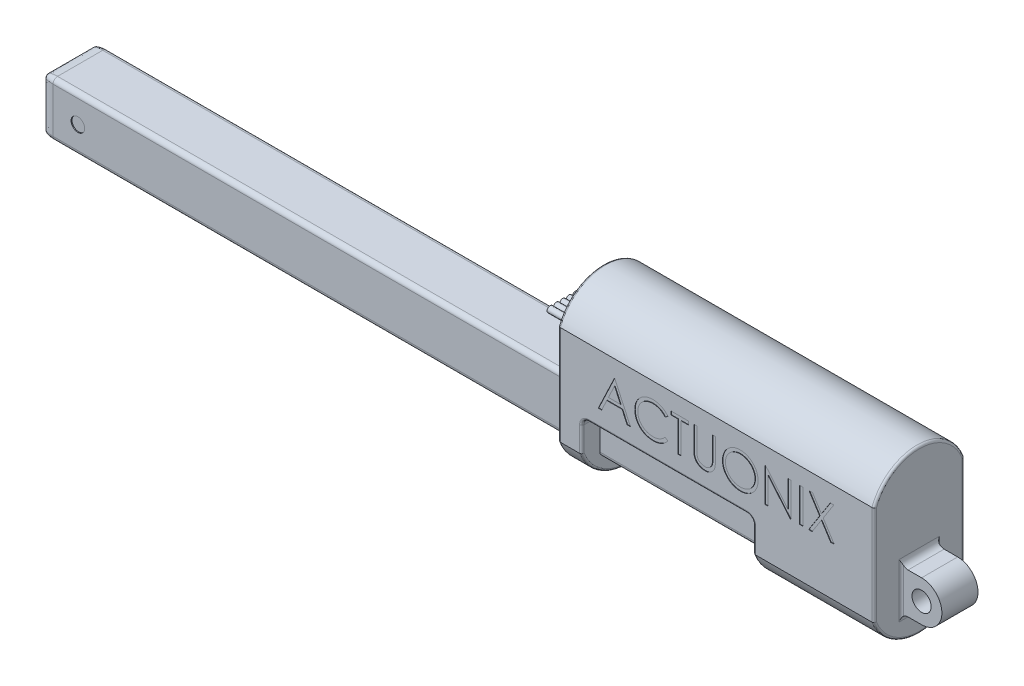
SolidWorks part; units mm, degrees
ref_plane "Front Plane" through (0, 0, 0) normal (0, 0, 1) x (1, 0, 0)
ref_plane "Top Plane" through (0, 0, 0) normal (0, 1, 0) x (1, 0, 0)
ref_plane "Right Plane" through (0, 0, 0) normal (1, 0, 0) x (0, 0, -1)
sketch "Sketch1" plane through (0, 0, 0) normal (0, 0, 1) x (1, 0, 0)
  line L0 (39.5, -12) -> (35, -12)
  line L1 (-35, 18) -> (35, 18)
  line L2 (-35, 18) -> (-35, -18)
  line L3 (-35, -18) -> (35, -18)
  line L4 (35, 18) -> (35, -3)
  line L5 (-35, 18) -> (35, -18) construction
  line L6 (-35, -18) -> (35, 18) construction
  line L7 (39.5, -3) -> (35, -3)
  line L8 (35, -12) -> (35, -18)
  circle A0 centre (39.5, -7.5) radius 2.125
  arc A1 (39.5, -12) -> (39.5, -3) centre (39.5, -7.5) ccw
  point P0 (0, 0)
  point P9 (44, -7.5)
  dimension "D3" = 4.25
  dimension "D5" = 4.5
  dimension "D1" = 70
  dimension "D2" = 36
  dimension "D4" = 10.5
  dimension "D6" = 4.5
extrude "Boss-Extrude1" add sketch "Sketch1" along normal mid plane 20
sketch "Sketch2" plane through (0, 18, 0) normal (0, 1, 0) x (1, 0, 0)
  line L1 (35, -10) -> (44, -10)
  line L2 (35, -10) -> (35, 10)
  line L3 (35, 10) -> (44, 10)
  line L4 (44, -10) -> (44, 10)
  line L5 (35, -4) -> (44, -4)
  line L6 (35, -4) -> (35, 4)
  line L7 (35, 4) -> (44, 4)
  line L8 (44, -4) -> (44, 4)
  line L9 (35, -4) -> (44, 4) construction
  line L10 (35, 4) -> (44, -4) construction
  point P6 (39.5, 0)
  point P11 (35, 0)
  line M12 (35, -10) -> (35, 10)
  dimension "D1" = 8
extrude "Cut-Extrude1" cut sketch "Sketch2" against normal through all contours L5 L1 L4 M12 | L7 L4 L3 M12 region at (39.5, 18, 7) region at (39.5, 18, -7)
sketch "Sketch3" plane through (0, 0, 10) normal (0, 0, 1) x (1, 0, 0)
  line L1 (-35, -18) -> (35, -18) construction
  line L2 (-29.75, -18) -> (-29.75, -13.5)
  line L3 (-29.75, -13.5) -> (8.25, -13.5)
  line L5 (8.25, -13.5) -> (8.25, -18)
  line L6 (-29.75, -18) -> (8.25, -18)
  line L7 (-35, 18) -> (-35, -18) construction
  dimension "D1" = 5.25
  dimension "D2" = 38
  dimension "D3" = 4.5
extrude "Cut-Extrude2" cut sketch "Sketch3" against normal through all contours L6 L5 L3 L2
sketch "Sketch4" plane through (0, -13.5, 0) normal (0, -1, 0) x (1, 0, 0)
  line L0 (8.25, -10) -> (8.25, 10) construction
  line L1 (-29.75, -10) -> (8.25, -10)
  line L2 (-29.75, -10) -> (-29.75, -6)
  line L3 (-29.75, -6) -> (8.25, -6)
  line L4 (8.25, -10) -> (8.25, -6)
  line L5 (-29.75, 0) -> (8.25, 0) construction
  line L6 (-29.75, 10) -> (8.25, 10)
  line L7 (-29.75, 10) -> (-29.75, 6)
  line L8 (-29.75, 6) -> (8.25, 6)
  line L9 (8.25, 10) -> (8.25, 6)
  line L10 (-29.75, -10) -> (-29.75, 10) construction
  dimension "D1" = 12
extrude "Cut-Extrude3" cut sketch "Sketch4" against normal blind 9.5
sketch "Sketch5" plane through (-35, 0, 0) normal (-1, 0, 0) x (0, 0, 1)
  line L0 (-6, -13.5) -> (6, -13.5) construction
  line L1 (-6, -13.5) -> (6, -13.5) construction
  line L2 (-6, -4) -> (-6, -13.5) construction
  line L3 (6, -4) -> (6, -13.5) construction
  line L4 (-6, -4) -> (-6, -13.5) construction
  line L5 (6, -4) -> (6, -13.5) construction
  line L6 (-6, -4) -> (-6, -1.5) construction
  line L7 (-6, -1.5) -> (6, -1.5) construction
  line L8 (6, -1.5) -> (6, -4) construction
  line L9 (-5.625, 3.375) -> (1.125, 3.375) construction
  line L10 (-5.625, 5.25) -> (1.125, 5.25)
  line L11 (-5.625, 1.5) -> (1.125, 1.5)
  line L12 (0, 18) -> (0, -1.5) construction
  line L13 (10, 18) -> (-10, 18) construction
  arc A0 (-5.625, 5.25) -> (-5.625, 1.5) centre (-5.625, 3.375) ccw
  arc A1 (1.125, 1.5) -> (1.125, 5.25) centre (1.125, 3.375) ccw
  point P8 (-2.25, 3.375)
  point P17 (3, 3.375)
  point P18 (-7.5, 3.375)
  dimension "D1" = 12
  dimension "D2" = 3
  dimension "D3" = 3
  dimension "D4" = 3.75
  dimension "D5" = 10.5
sketch "Sketch6" plane through (35, 0, 0) normal (1, 0, 0) x (0, 0, -1)
  line L0 (0, 18) -> (0, -3.0686) construction
  line L1 (-10, 18) -> (10, 18) construction
  line L2 (-10, 18) -> (-10, 11) construction
  line L3 (-10, -18) -> (-10, 18) construction
  line L4 (10, -18) -> (10, 18) construction
  arc A0 (-10, 11) -> (10, 11) centre (0, 7.3571) cw
  line M5 (10, 18) -> (-10, 18)
  line M6 (-10, 18) -> (-10, -18)
  line M8 (10, -18) -> (10, 18)
  dimension "D1" = 7
extrude "Cut-Extrude4" cut sketch "Sketch6" against normal through all and the other way through all contours A0 M6 M5 | A0 M5 M8 region at (35, 16.112, 7.6911) region at (35, 16.112, -7.6911)
sketch "Sketch7" plane through (35, 0, 0) normal (1, 0, 0) x (0, 0, -1)
  line L0 (0, 0) -> (-10, 0) construction
  line L1 (-10, -18) -> (-10, 11) construction
  line L2 (10, -18) -> (10, 11) construction
  line L4 (-10, -11) -> (-10, -18)
  line L5 (-10, -18) -> (10, -18)
  line L6 (10, -18) -> (10, -11)
  arc A0 (10, 11) -> (-10, 11) centre (0, 7.3571) ccw construction
  arc A2 (10, -11) -> (-10, -11) centre (0, -7.3571) cw
  line M5 (10, -18) -> (10, 11)
  line M7 (-10, 11) -> (-10, -18)
  line M8 (-10, -18) -> (10, -18)
extrude "Cut-Extrude5" cut sketch "Sketch7" against normal through all contours A2 M8 M7 | A2 L5 M5 region at (35, -16.112, 7.6911) region at (35, -16.112, -7.6911)
extrude "Boss-Extrude2" add sketch "Sketch5" along normal blind 4.31 separate body
sketch "Sketch8" plane through (-39.31, 0, 0) normal (-1, 0, 0) x (0, 0, 1)
  circle A0 centre (-5.625, 3.375) radius 0.675
  circle A1 centre (-4.225, 3.375) radius 0.675
  circle A2 centre (-2.825, 3.375) radius 0.675
  circle A3 centre (-1.425, 3.375) radius 0.675
  circle A4 centre (-0.025, 3.375) radius 0.675
  dimension "D1" = 1.35
  dimension "D2" = 1.4
  dimension "D3" = 1.4
  dimension "D4" = 1.4
  dimension "D5" = 1.4
extrude "Boss-Extrude3" add sketch "Sketch8" along normal blind 7.5 separate body
sketch "Sketch9" plane through (-35, 0, 0) normal (-1, 0, 0) x (0, 0, 1)
  line L0 (-6, -4) -> (-6, -1.5) construction
  line L1 (-6, -4) -> (-6, -13.5) construction
  line L2 (-6, -13.5) -> (6, -13.5) construction
  line L3 (6, -4) -> (6, -13.5) construction
  line L4 (6, -1.5) -> (6, -4) construction
  line L5 (-6, -1.5) -> (6, -1.5) construction
  line L6 (-6, -4) -> (-6, -2.5)
  line L7 (-6, -4) -> (-6, -12.5)
  line L8 (-5, -13.5) -> (5, -13.5)
  line L9 (6, -4) -> (6, -12.5)
  line L10 (6, -2.5) -> (6, -4)
  line L11 (-5, -1.5) -> (5, -1.5)
  arc A0 (-6, -12.5) -> (-5, -13.5) centre (-5, -12.5) ccw
  arc A1 (5, -13.5) -> (6, -12.5) centre (5, -12.5) ccw
  arc A2 (6, -2.5) -> (5, -1.5) centre (5, -2.5) ccw
  arc A3 (-6, -2.5) -> (-5, -1.5) centre (-5, -2.5) cw
  dimension "D1" = 1
extrude "Boss-Extrude4" add sketch "Sketch9" along normal blind 117.9 separate body
sketch "Sketch10" plane through (-152.9, 0, 0) normal (-1, 0, 0) x (0, 0, 1)
  line L0 (0, -1.5) -> (0, -13.5) construction
  line L1 (5, -1.5) -> (-5, -1.5) construction
  line L2 (-5, -13.5) -> (5, -13.5) construction
  circle A0 centre (0, -7.5) radius 4.5
  dimension "D1" = 9
extrude "Cut-Extrude6" cut sketch "Sketch10" against normal blind 50
sketch "Sketch12" plane through (0, 0, 10) normal (0, 0, 1) x (1, 0, 0)
  line L0 (-35, -0.25) -> (35, -0.25) construction
  line L1 (-35, 11) -> (-35, -11) construction
  line L2 (35, -11) -> (35, 11) construction
  line L3 (8.25, -4) -> (-29.75, -4) construction
  text T0 "ACTUONIX" font "Century Gothic" height 7.5
  dimension "D1" = 3.75
extrude "Cut-Extrude7" cut sketch "Sketch12" against normal blind 0.1
sketch "Sketch13" plane through (0, 0, -10) normal (0, 0, -1) x (-1, 0, 0)
  line L0 (35, -0.25) -> (-35, -0.25) construction
  line L1 (35, -0.25) -> (-35, -0.25) construction
  line L2 (-35, 7.25) -> (35, 7.25) construction
  line L3 (-35, -11) -> (-35, 11) construction
  line L4 (35, 11) -> (35, -11) construction
  text T0 "ACTUONIX" font "Century Gothic" height 7.5
  dimension "D1" = 7.5
extrude "Cut-Extrude8" cut sketch "Sketch13" against normal blind 0.1
fillet "Fillet1" radius 2 8 edges at (-152.9, -13.5, 0) (-152.9, -7.5, 6) (-152.9, -1.5, 0) (-152.9, -7.5, -6) (-152.9, -1.7929, 5.7071) (-152.9, -13.2071, 5.7071) (-152.9, -1.7929, -5.7071) (-152.9, -13.2071, -5.7071) second distance 0.5 first distance on face at (-93.95, -13.5, 0) first distance on face at (-93.95, -7.5, 6) first distance on face at (-93.95, -1.5, 0) first distance on face at (-93.95, -7.5, -6) first distance on face at (-93.95, -1.8964, 5.6036) first distance on face at (-93.95, -13.1036, 5.6036) first distance on face at (-93.95, -1.8964, -5.6036) first distance on face at (-93.95, -13.1036, -5.6036)
sketch "Sketch14" plane through (0, 0, 6) normal (0, 0, 1) x (1, 0, 0)
  line L0 (-150.9, -7.5) -> (-35, -7.5) construction
  line L1 (-150.9, -2.5) -> (-150.9, -12.5) construction
  line L2 (-35, -12.5) -> (-35, -2.5) construction
  circle A0 centre (-145.4, -7.5) radius 1.5
  dimension "D1" = 3
  dimension "D2" = 5.5
extrude "Cut-Extrude9" cut sketch "Sketch14" against normal blind 0.2
sketch "Sketch15" plane through (0, 0, -6) normal (0, 0, -1) x (-1, 0, 0)
  circle A1 centre (145.4, -7.5) radius 1.5
  circle A2 centre (145.4, -7.5) radius 1.5
  dimension "D1" = 0
extrude "Cut-Extrude10" cut sketch "Sketch15" against normal blind 0.2
fillet "Fillet2" radius 1.5 4 edges at (-29.75, -4, 8) (-29.75, -4, -8) (8.25, -4, -8) (8.25, -4, 8)
fillet "Fillet3" radius 1.5 2 edges at (35, -3, 0) (35, -12, 0)
fillet "Fillet4" radius 0.5 2 edges at (35, -7.5, 4) (35, -7.5, -4)
fillet "Fillet5" radius 1 2 edges at (-10.75, -13.5, -6) (-10.75, -13.5, 6)
fillet "Fillet6" radius 0.5 20 edges at (-29.75, -8.25, 10) (-29.3107, -4.4393, 10) (-10.75, -4, 10) (7.8107, -4.4393, 10) (8.25, -8.25, 10) (8.25, -18, 0) (7.8107, -4.4393, -10) (8.25, -8.25, -10) (-10.75, -4, -10) (-29.3107, -4.4393, -10) (-29.75, -8.25, -10) (-29.75, -18, 0) (35, 0, 10) (35, 18, 0) (35, 0, -10) (35, -18, 0) (-35, -18, 0) (-35, 0, -10) (-35, 18, 0) (-35, 0, 10)
